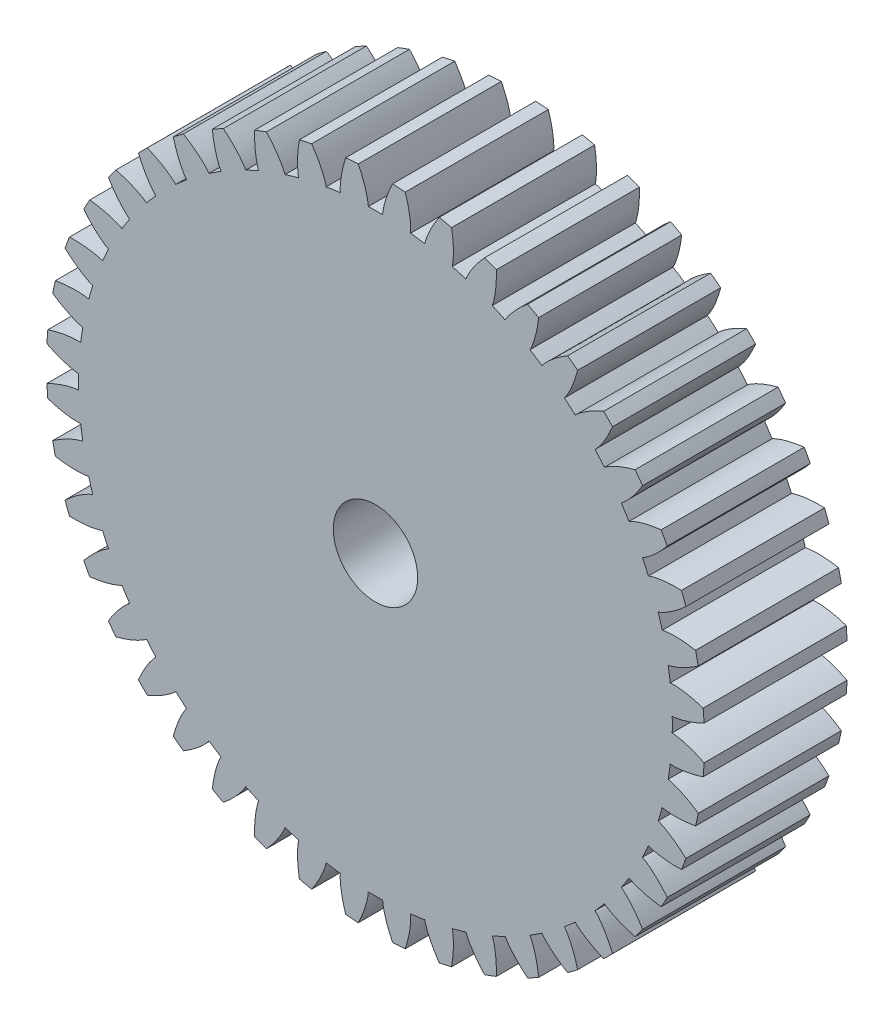
SolidWorks part; units mm, degrees
ref_plane "前视基准面" through (0, 0, 0) normal (0, 0, 1) x (1, 0, 0)
ref_plane "上视基准面" through (0, 0, 0) normal (0, 1, 0) x (1, 0, 0)
ref_plane "右视基准面" through (0, 0, 0) normal (1, 0, 0) x (0, 0, -1)
other "Configuration Table"
sketch "草图1" plane through (0, 0, 0) normal (0, 0, 1) x (1, 0, 0)
  line L0 (0, 0) -> (11, 0) construction
  line L1 (0, 0) -> (10.993, 0.3926) construction
  line L2 (0, 0) -> (10.3336, 0.2483)
  line L3 (10.993, 0.3926) -> (10.993, -0.3926) construction
  line L4 (0, 0) -> (10.3336, -0.2483)
  circle A0 centre (0, 0) radius 11.5
  circle A1 centre (0, 0) radius 11 construction
  circle A2 centre (0, 0) radius 10.375
  circle A3 centre (0, 0) radius 10.3366 construction
  circle A4 centre (0, 0) radius 1.475
  spline S0 degree 4 poles (10.3336, 0.2483) (10.373, 0.2492) (10.4514, 0.2548) (10.5993, 0.2786) (10.8137, 0.3309) (11.176, 0.4502) (11.727, 0.7039) (12.4175, 1.1418) (13.2845, 1.8857) (14.159, 2.8996) (14.9497, 4.1399) (15.6089, 5.5809) (16.0848, 7.0915) (16.3869, 8.6457) (16.5318, 10.3005) (16.4965, 12.3573) (16.1403, 14.7881) (15.3183, 17.523) (13.9467, 20.3832) (12.179, 23.0152) (10.073, 25.3838) (7.9816, 27.2037) (6.0426, 28.5725) (4.3439, 29.5825) (2.9407, 30.3111) (1.4991, 30.9596) (0.0233, 31.5277) (-1.8557, 32.137) (-3.7766, 32.6124) (-5.5266, 32.9201) (-7.002, 33.0904) (-7.7836, 33.1582) (-8.3173, 33.1949) (-8.735, 33.2194) (-9.3275, 33.2428) (-9.7696, 33.2534) (-10.4973, 33.2604) (-11.0568, 33.25) (-11.7417, 33.2305) (-12.3487, 33.1968) (-13.0045, 33.1521) (-13.6246, 33.0946) (-14.1115, 33.043) (-14.4211, 33.0043) (-14.582, 32.9841) knots 0 0 0 0 0 0.002802 0.005604 0.010661 0.015718 0.02996 0.048734 0.068727 0.096889 0.125051 0.153212 0.181374 0.209535 0.237696 0.271429 0.327752 0.384075 0.440398 0.496721 0.553044 0.609367 0.637529 0.66569 0.693852 0.722013 0.750174 0.778336 0.834659 0.86282 0.876901 0.883942 0.890982 0.900036 0.909091 0.920455 0.931818 0.943182 0.954545 0.965909 0.977273 0.988636 1 1 1 1 1 construction
  spline S1 degree 4 poles (10.3336, 0.2483) (10.373, 0.2492) (10.4514, 0.2548) (10.5993, 0.2786) (10.8137, 0.3309) (11.176, 0.4502) (11.727, 0.7039) (12.4175, 1.1418) (13.2845, 1.8857) (14.159, 2.8996) (14.9497, 4.1399) (15.6089, 5.5809) (16.0848, 7.0915) (16.3869, 8.6457) (16.5318, 10.3005) (16.4965, 12.3573) (16.1403, 14.7881) (15.3183, 17.523) (13.9467, 20.3832) (12.179, 23.0152) (10.073, 25.3838) (7.9816, 27.2037) (6.0426, 28.5725) (4.3439, 29.5825) (2.9407, 30.3111) (1.4991, 30.9596) (0.0233, 31.5277) (-1.8557, 32.137) (-3.7766, 32.6124) (-5.5266, 32.9201) (-7.002, 33.0904) (-7.7836, 33.1582) (-8.3173, 33.1949) (-8.735, 33.2194) (-9.1431, 33.2355) (-9.3769, 33.2429) (-9.4923, 33.2458) knots 0 0 0 0 0 0.002802 0.005604 0.010661 0.015718 0.02996 0.048734 0.068727 0.096889 0.125051 0.153212 0.181374 0.209535 0.237696 0.271429 0.327752 0.384075 0.440398 0.496721 0.553044 0.609367 0.637529 0.66569 0.693852 0.722013 0.750174 0.778336 0.834659 0.86282 0.876901 0.883942 0.890982 0.900036 0.909091 0.909091 0.909091 0.909091 0.909091
  spline S2 degree 4 poles (10.3336, -0.2483) (10.373, -0.2492) (10.4514, -0.2548) (10.5993, -0.2786) (10.8137, -0.3309) (11.176, -0.4502) (11.727, -0.7039) (12.4175, -1.1418) (13.2845, -1.8857) (14.159, -2.8996) (14.9497, -4.1399) (15.6089, -5.5809) (16.0848, -7.0915) (16.3869, -8.6457) (16.5318, -10.3005) (16.4965, -12.3573) (16.1403, -14.7881) (15.3183, -17.523) (13.9467, -20.3832) (12.179, -23.0152) (10.073, -25.3838) (7.9816, -27.2037) (6.0426, -28.5725) (4.3439, -29.5825) (2.9407, -30.3111) (1.4991, -30.9596) (0.0233, -31.5277) (-1.8557, -32.137) (-3.7766, -32.6124) (-5.5266, -32.9201) (-7.002, -33.0904) (-7.7836, -33.1582) (-8.3173, -33.1949) (-8.735, -33.2194) (-9.3275, -33.2428) (-9.7696, -33.2534) (-10.4973, -33.2604) (-11.0568, -33.25) (-11.7417, -33.2305) (-12.3487, -33.1968) (-13.0045, -33.1521) (-13.6246, -33.0946) (-14.1115, -33.043) (-14.4211, -33.0043) (-14.582, -32.9841) knots 0 0 0 0 0 0.002802 0.005604 0.010661 0.015718 0.02996 0.048734 0.068727 0.096889 0.125051 0.153212 0.181374 0.209535 0.237696 0.271429 0.327752 0.384075 0.440398 0.496721 0.553044 0.609367 0.637529 0.66569 0.693852 0.722013 0.750174 0.778336 0.834659 0.86282 0.876901 0.883942 0.890982 0.900036 0.909091 0.920455 0.931818 0.943182 0.954545 0.965909 0.977273 0.988636 1 1 1 1 1 construction
  spline S3 degree 4 poles (10.3336, -0.2483) (10.373, -0.2492) (10.4514, -0.2548) (10.5993, -0.2786) (10.8137, -0.3309) (11.176, -0.4502) (11.727, -0.7039) (12.4175, -1.1418) (13.2845, -1.8857) (14.159, -2.8996) (14.9497, -4.1399) (15.6089, -5.5809) (16.0848, -7.0915) (16.3869, -8.6457) (16.5318, -10.3005) (16.4965, -12.3573) (16.1403, -14.7881) (15.3183, -17.523) (13.9467, -20.3832) (12.179, -23.0152) (10.073, -25.3838) (7.9816, -27.2037) (6.0426, -28.5725) (4.3439, -29.5825) (2.9407, -30.3111) (1.4991, -30.9596) (0.0233, -31.5277) (-1.8557, -32.137) (-3.7766, -32.6124) (-5.5266, -32.9201) (-7.002, -33.0904) (-7.7836, -33.1582) (-8.3173, -33.1949) (-8.735, -33.2194) (-9.1431, -33.2355) (-9.3769, -33.2429) (-9.4923, -33.2458) knots 0 0 0 0 0 0.002802 0.005604 0.010661 0.015718 0.02996 0.048734 0.068727 0.096889 0.125051 0.153212 0.181374 0.209535 0.237696 0.271429 0.327752 0.384075 0.440398 0.496721 0.553044 0.609367 0.637529 0.66569 0.693852 0.722013 0.750174 0.778336 0.834659 0.86282 0.876901 0.883942 0.890982 0.900036 0.909091 0.909091 0.909091 0.909091 0.909091
  point P15 (10.993, 0)
  dimension "齿顶圆直径" = 23
  dimension "分度圆直径" = 22
  dimension "齿根圆直径" = 20.75
  dimension "基圆直径" = 20.6732
  dimension "内孔直径" = 2.95
  dimension "渐近线镜像线夹角" = 2.045
extrude "凸台-拉伸1" add sketch "草图1" along normal blind 5 contours A0 | A4
extrude "切除-拉伸1" cut sketch "草图1<3>" along normal through all contours A2 S3 A0 S1 region at (11.0211, 0, 0)
sketch "草图1<3>" plane through (0, 0, 0) normal (0, 0, 1) x (1, 0, 0) same geometry as "草图1"
pattern_circular "阵列(圆周)1" count 44 every 8.182 about axis through (0, 0, 5) along (0, 0, 1) of "切除-拉伸1"
equation "\"m\"= 0.5'模数"
equation "\"z\"= 44'齿数"
equation "\"a\"= 20度'压力角"
equation "\"d\"= \"m\" * \"z\"'分度圆直径"
equation "\"da\"= ( \"z\" + 2 ) * \"m\"'齿顶圆直径"
equation "\"df\"= ( \"z\" - 2.5 ) * \"m\"'齿根圆直径"
equation "\"s\"= 0.5 * PI * \"m\"'分度圆齿厚"
equation "\"r\"= 0.38 * \"m\"'齿根圆角"
equation "\"B\"= 0.3 * \"d\"'齿厚"
equation "\"db\"= \"m\" * \"z\" * cos ( \"a\" )'基圆直径"
equation "\"rb\"= \"db\" / 2'基圆半径"
equation "\"齿顶圆直径@草图1\"= \"da\""
equation "\"分度圆直径@草图1\"= \"d\""
equation "\"齿根圆直径@草图1\"= \"df\""
equation "\"基圆直径@草图1\"= \"db\""
equation "\"渐近线镜像线夹角@草图1\"= 360 / 4 / \"z\""
equation "\"h\"= 5'齿轮厚度"
equation "\"ir\"= 2.95'内孔直径"
equation "\"内孔直径@草图1\"= \"ir\""
equation "\"齿轮厚@凸台-拉伸1\"= \"h\""
equation "\"齿轮夹角@阵列(圆周)1\"= 360 / \"z\""
equation "\"齿数@阵列(圆周)1\"= \"z\""
